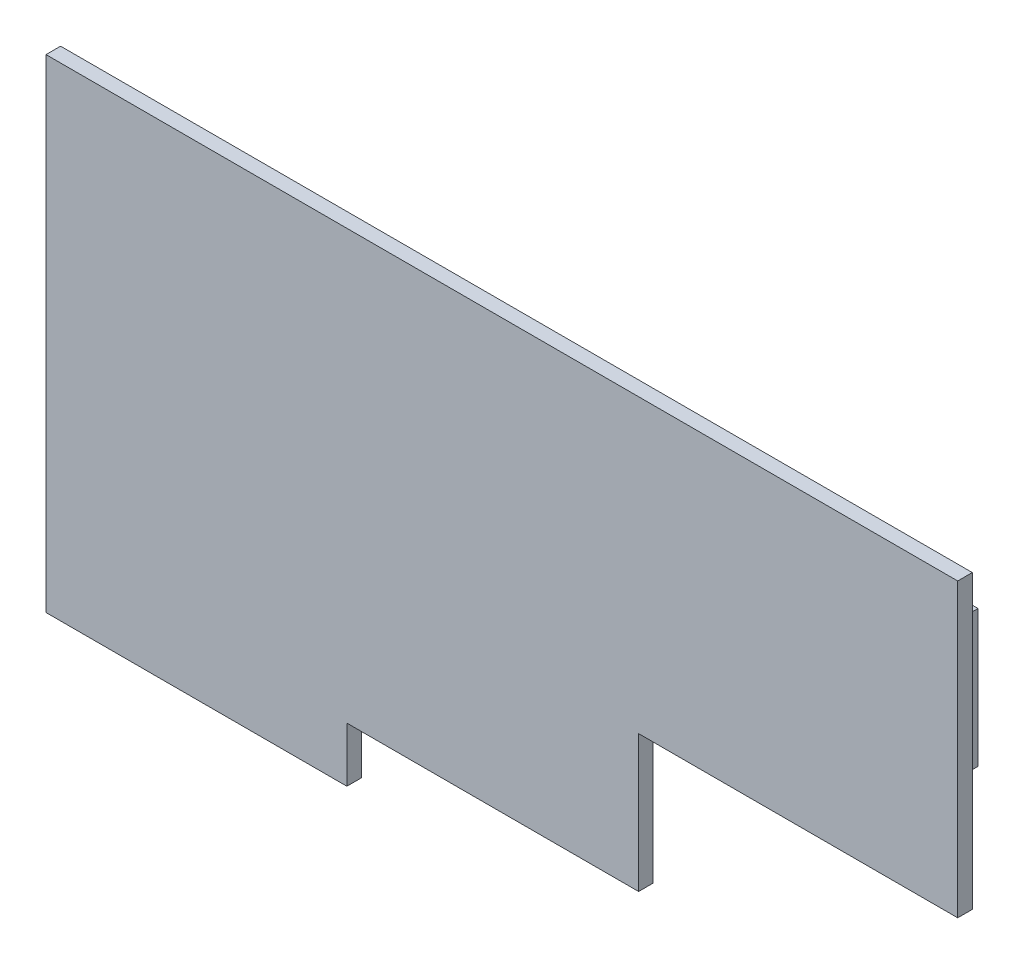
SolidWorks part; units mm, degrees
ref_plane "Front Plane" through (0, 0, 0) normal (0, 0, 1) x (1, 0, 0)
ref_plane "Top Plane" through (0, 0, 0) normal (0, 1, 0) x (1, 0, 0)
ref_plane "Right Plane" through (0, 0, 0) normal (1, 0, 0) x (0, 0, -1)
sketch "Sketch1" plane through (0, 0, 0) normal (0, 0, 1) x (1, 0, 0)
  line L0 (33, -53) -> (33, -47)
  line L1 (0, 0) -> (33, 0)
  line L2 (0, 0) -> (0, -53)
  line L3 (0, -53) -> (33, -53)
  line L4 (65, -47) -> (65, -32)
  line L5 (65, -47) -> (33, -47)
  line L7 (65, 0) -> (33, 0)
  line L9 (65, 0) -> (100, 0)
  line L11 (65, -32) -> (100, -32)
  line L12 (100, 0) -> (100, -32)
  dimension "D1" = 53
  dimension "D2" = 33
  dimension "D3" = 47
  dimension "D4" = 32
  dimension "D5" = 32
  dimension "D6" = 35
extrude "Boss-Extrude1" add sketch "Sketch1" along normal blind 1.6
sketch "Sketch2" plane through (0, 0, 0) normal (0, 0, -1) x (-1, 0, 0)
  line L0 (-100, 0) -> (0, 0) construction
  line L1 (-93.625, -10.1) -> (-88.625, -10.1)
  line L2 (-93.625, -10.1) -> (-93.625, -25.1)
  line L3 (-93.625, -25.1) -> (-88.625, -25.1)
  line L4 (-88.625, -10.1) -> (-88.625, -25.1)
  line L5 (-100, -32) -> (-100, 0) construction
  dimension "D1" = 5
  dimension "D2" = 15
  dimension "D3" = 10.1
  dimension "D4" = 6.375
extrude "Boss-Extrude2" add sketch "Sketch2" along normal blind 7
